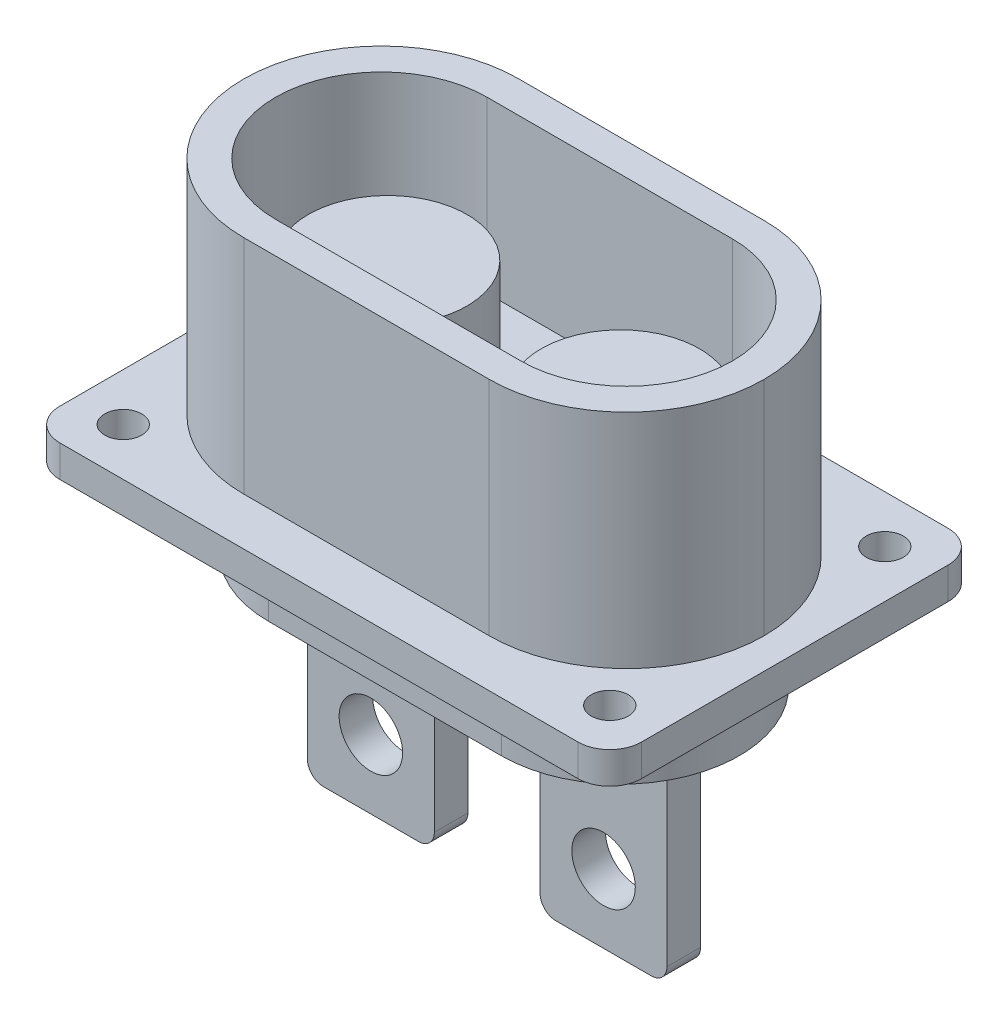
SolidWorks part; units mm, degrees
material "Custom Plastic"
ref_plane "X-Y Datum" through (0, 0, 0) normal (0, 0, 1) x (1, 0, 0)
ref_plane "X-Z Datum" through (0, 0, 0) normal (0, 1, 0) x (1, 0, 0)
ref_plane "Y-Z Datum" through (0, 0, 0) normal (1, 0, 0) x (0, 0, -1)
sketch "Sketch1" plane through (0, 0, 0) normal (0, 1, 0) x (1, 0, 0)
  line L0 (-23, 13) -> (23, 13)
  line L1 (-27.5, 17.5) -> (27.5, 17.5)
  line L2 (-27.5, 17.5) -> (-27.5, -17.5)
  line L3 (-27.5, -17.5) -> (27.5, -17.5)
  line L4 (27.5, 17.5) -> (27.5, -17.5)
  line L5 (-27.5, 17.5) -> (27.5, -17.5) construction
  line L6 (-27.5, -17.5) -> (27.5, 17.5) construction
  line L7 (-23, 13) -> (-23, -13)
  line L8 (0, 11.5231) -> (0, -11.5231) construction
  circle A0 centre (-23, 13) radius 1.75
  circle A1 centre (-23, -13) radius 1.75
  circle A2 centre (23, -13) radius 1.75
  circle A3 centre (23, 13) radius 1.75
  point P0 (0, 0)
  point P9 (0, 13)
  point P13 (-23, 0)
  point P16 (0, 0)
  dimension "D5" = 3.5
  dimension "D1" = 55
  dimension "D2" = 35
  dimension "D3" = 46
  dimension "D4" = 26
extrude "Boss-Extrude1" add sketch "Sketch1" along normal blind 3 contours L4 L1 L2 L3 A2 A3 A0 A1 region at (0, 0, 0)
fillet "Fillet1" radius 3 4 edges at (-27.5, 1.5, 17.5) (-27.5, 1.5, -17.5) (27.5, 1.5, -17.5) (27.5, 1.5, 17.5)
sketch "Sketch2" plane through (0, 3, 0) normal (0, 1, 0) x (1, 0, 0)
  line L1 (-24.6, 13) -> (24.6, 13)
  line L2 (-24.6, 13) -> (-24.6, -13)
  line L3 (-24.6, -13) -> (24.6, -13)
  line L4 (24.6, 13) -> (24.6, -13)
  line L5 (-24.6, 13) -> (24.6, -13) construction
  line L6 (-24.6, -13) -> (24.6, 13) construction
  point P0 (0, 0)
  dimension "D1" = 49.2
  dimension "D2" = 26
extrude "Boss-Extrude2" add sketch "Sketch2" along normal blind 21
fillet "Fillet2" radius 13 4 edges at (-24.6, 13.5, 13) (-24.6, 13.5, -13) (24.6, 13.5, -13) (24.6, 13.5, 13)
sketch "Sketch3" plane through (0, 0, 0) normal (0, -1, 0) x (1, 0, 0)
  line L0 (-27.5, 0) -> (27.5, 0)
  line L1 (-27.5, -14.5) -> (-27.5, 14.5) construction
  line L2 (27.5, -14.5) -> (27.5, 14.5) construction
  line L3 (-11, 0) -> (11, 0)
  line L4 (-17, 1.5875) -> (-5, 1.5875)
  line L5 (-17, 1.5875) -> (-17, -1.5875)
  line L6 (-17, -1.5875) -> (-5, -1.5875)
  line L7 (-5, 1.5875) -> (-5, -1.5875)
  line L8 (-17, 1.5875) -> (-5, -1.5875) construction
  line L9 (-17, -1.5875) -> (-5, 1.5875) construction
  line L10 (5, 1.5875) -> (17, 1.5875)
  line L11 (5, 1.5875) -> (5, -1.5875)
  line L12 (5, -1.5875) -> (17, -1.5875)
  line L13 (17, 1.5875) -> (17, -1.5875)
  line L14 (5, 1.5875) -> (17, -1.5875) construction
  line L15 (5, -1.5875) -> (17, 1.5875) construction
  point P6 (-11, 0)
  point P11 (11, 0)
  point P19 (0, 0)
  dimension "D1" = 22
  dimension "D3" = 12
  dimension "D4" = 3.175
extrude "Boss-Extrude3" add sketch "Sketch3" along normal blind 28.6 contours L7 L0 L5 L6 | L7 L4 L5 L0 | L13 L10 L11 L0 | L13 L0 L11 L12 region at (-11, 0, 0.7937) region at (11, 0, 0.7938) region at (11, 0, -0.7937) region at (-11, 0, -0.7937)
sketch "Sketch4" plane through (0, 0, 1.5875) normal (0, 0, 1) x (1, 0, 0)
  line L0 (-11, 0) -> (-11, -28.6) construction
  line L1 (-17, 0) -> (-5, 0) construction
  line L2 (-17, -28.6) -> (-5, -28.6) construction
  line L3 (-24.5, 0) -> (24.5, 0) construction
  circle A0 centre (-11, -22.1) radius 3
  dimension "D1" = 6
  dimension "D2" = 22.1
extrude "Cut-Extrude1" cut sketch "Sketch4" against normal through all
mirror "Mirror1" about plane through (0, 0, 0) normal (1, 0, 0) of "Cut-Extrude1"
sketch "Sketch5" plane through (0, 24, 0) normal (0, 1, 0) x (1, 0, 0)
  line L4 (-11.6, -10) -> (11.6, -10)
  line L5 (11.6, 10) -> (-11.6, 10)
  line L6 (-11.6, -10) -> (11.6, -10)
  line L7 (11.6, 10) -> (-11.6, 10)
  arc A8 (-11.6, 10) -> (-21.6, 0) centre (-11.6, 0) ccw
  arc A9 (-21.6, 0) -> (-11.6, -10) centre (-11.6, 0) ccw
  arc A10 (11.6, -10) -> (21.6, 0) centre (11.6, 0) ccw
  arc A11 (21.6, 0) -> (11.6, 10) centre (11.6, 0) ccw
  arc A12 (-11.6, 10) -> (-21.6, 0) centre (-11.6, 0) ccw
  arc A13 (-21.6, 0) -> (-11.6, -10) centre (-11.6, 0) ccw
  arc A14 (11.6, -10) -> (21.6, 0) centre (11.6, 0) ccw
  arc A15 (21.6, 0) -> (11.6, 10) centre (11.6, 0) ccw
  dimension "D1" = 3
extrude "Cut-Extrude2" cut sketch "Sketch5" against normal blind 16.05
sketch "Sketch6" plane through (0, 0, 0) normal (0, -1, 0) x (1, 0, 0)
  line L0 (11, 11.25) -> (-11, 11.25)
  line L1 (-11, -11.25) -> (11, -11.25)
  line L2 (0, 11.25) -> (0, -11.25) construction
  line L3 (-22.1777, 0) -> (22.1777, 0) construction
  line L6 (11, 11.25) -> (11, -11.25)
  line L7 (-11, 11.25) -> (-11, -11.25)
  circle A5 centre (11, 0) radius 11.25
  circle A6 centre (-11, 0) radius 11.25
  point P5 (0, 0)
  point P6 (0, 0)
  line M7 (5, 1.5875) -> (17, 1.5875)
  line M8 (17, 1.5875) -> (17, -1.5875)
  line M9 (17, -1.5875) -> (5, -1.5875)
  line M10 (5, -1.5875) -> (5, 1.5875)
  line M11 (-17, 1.5875) -> (-5, 1.5875)
  line M12 (-5, 1.5875) -> (-5, -1.5875)
  line M13 (-5, -1.5875) -> (-17, -1.5875)
  line M14 (-17, -1.5875) -> (-17, 1.5875)
  dimension "D4" = 22.5
  dimension "D3" = 22
  dimension "D1" = 22
extrude "Boss-Extrude4" add sketch "Sketch6" along normal blind 8 contours L7 A6 M13 M14 M11 | L7 A6 A5 M11 M12 M13 | A6 A5 L6 M9 M10 M7 | L6 A5 M7 M8 M9 | A6 A5 L0 | A6 L1 A5 | A5 A6 region at (0, 0, 8.9659) region at (18.7771, 0, 7.7771) region at (10.7496, 0, 6.4188) region at (-4.0853, 0, 8.5544) region at (-11.2516, 0, 6.4188) region at (0, 0, 0) region at (0, 0, -8.9659)
sketch "Sketch7" plane through (0, 7.95, 0) normal (0, 1, 0) x (1, 0, 0)
  line L0 (-11, 0) -> (11, 0)
  circle A0 centre (-11, 0) radius 7.5
  circle A1 centre (11, 0) radius 7.5
  point P8 (0, 0)
  dimension "D1" = 15
  dimension "D2" = 22
extrude "Boss-Extrude5" add sketch "Sketch7" along normal blind 8 contours A0 | A1 region at (11, 7.95, -7.2879) region at (-18.2879, 7.95, 0)
fillet "Fillet3" radius 1.5 4 edges at (17, -28.6, 0) (5, -28.6, 0) (-5, -28.6, 0) (-17, -28.6, 0)
